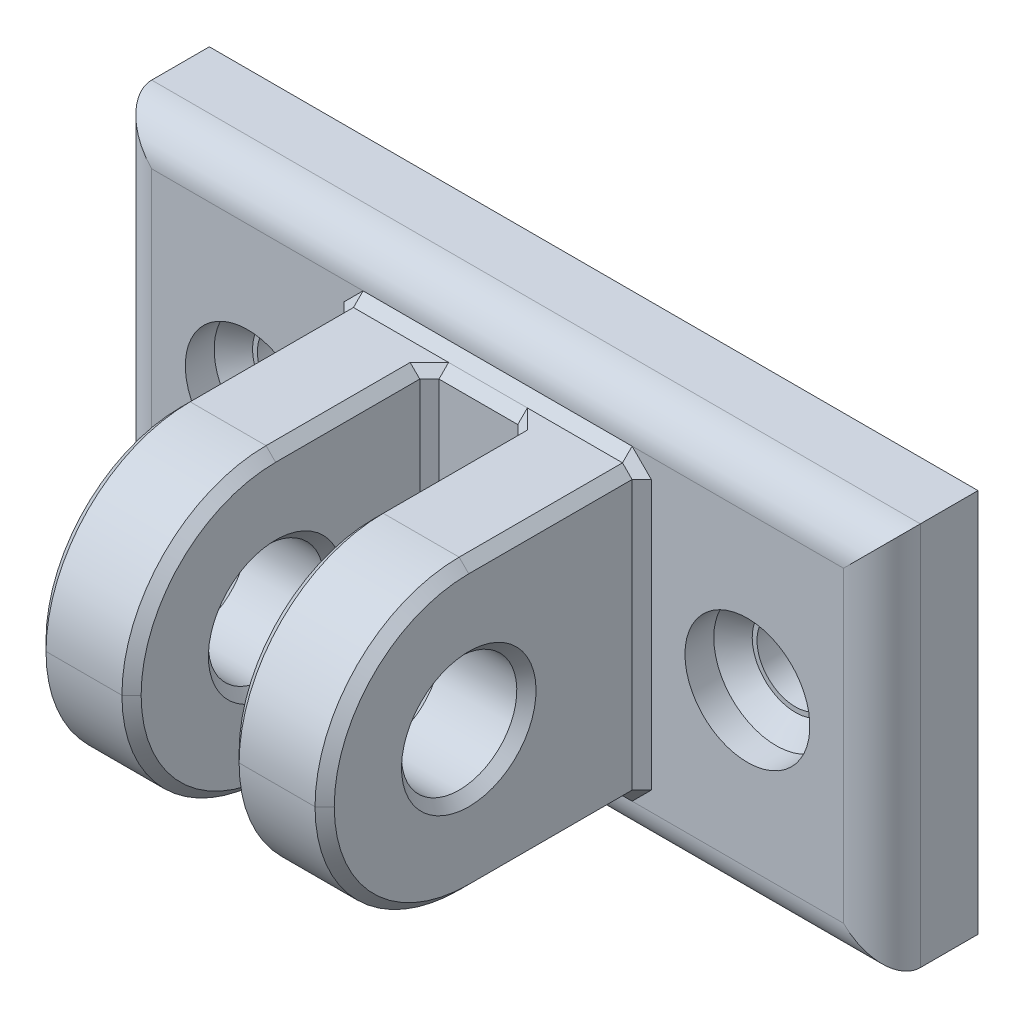
SolidWorks part; units mm, degrees
ref_plane "Front Plane" through (0, 0, 0) normal (0, 0, 1) x (1, 0, 0)
ref_plane "Top Plane" through (0, 0, 0) normal (0, 1, 0) x (1, 0, 0)
ref_plane "Right Plane" through (0, 0, 0) normal (1, 0, 0) x (0, 0, -1)
sketch "Sketch1" plane through (0, 0, 0) normal (0, 0, 1) x (1, 0, 0)
  line L1 (20, 10) -> (-20, 10)
  line L2 (20, 10) -> (20, -10)
  line L3 (20, -10) -> (-20, -10)
  line L4 (-20, 10) -> (-20, -10)
  line L5 (20, 10) -> (-20, -10) construction
  line L6 (20, -10) -> (-20, 10) construction
  point P0 (0, 0)
  dimension "D1" = 20
  dimension "D2" = 40
extrude "Boss-Extrude1" add sketch "Sketch1" along normal blind 5
sketch "Sketch2" plane through (0, 0, 5) normal (0, 0, 1) x (1, 0, 0)
  line L0 (0, 5.7785) -> (0, -5.0624) construction
  line L1 (7.5, -7.5) -> (2.55, 7.5) construction
  line L2 (-7.5, 7.5) -> (-2.55, 7.5)
  line L3 (-7.5, 7.5) -> (-7.5, -7.5)
  line L4 (-7.5, -7.5) -> (-2.55, -7.5)
  line L5 (-2.55, 7.5) -> (-2.55, -7.5)
  line L6 (-7.5, 7.5) -> (-2.55, -7.5) construction
  line L7 (-7.5, -7.5) -> (-2.55, 7.5) construction
  line L8 (7.5, 7.5) -> (2.55, -7.5) construction
  line L9 (2.55, 7.5) -> (2.55, -7.5)
  line L10 (7.5, -7.5) -> (2.55, -7.5)
  line L11 (7.5, 7.5) -> (7.5, -7.5)
  line L12 (7.5, 7.5) -> (2.55, 7.5)
  point P1 (-5.025, 0)
  dimension "D1" = 2.55
  dimension "D2" = 7.5
  dimension "D3" = 15
  dimension "D4" = 0
extrude "Boss-Extrude2" add sketch "Sketch2" along normal blind 16.5
sketch "Sketch3" plane through (-7.5, 0, 0) normal (-1, 0, 0) x (0, 0, 1)
  line L0 (21.5, 7.5) -> (21.5, -7.5) construction
  circle A0 centre (14, 0) radius 3
  dimension "D1" = 6
  dimension "D2" = 7.5
extrude "Cut-Extrude1" cut sketch "Sketch3" against normal through all both and the other way through all
fillet "Fillet1" radius 7.5 4 edges at (5.025, -7.5, 21.5) (5.025, 7.5, 21.5) (-5.025, -7.5, 21.5) (-5.025, 7.5, 21.5)
sketch "Sketch4" plane through (0, 0, 5) normal (0, 0, 1) x (1, 0, 0)
  line L1 (2.55, 7.5) -> (-2.55, 7.5)
  line L2 (2.55, 7.5) -> (2.55, -7.5)
  line L3 (2.55, -7.5) -> (-2.55, -7.5)
  line L4 (-2.55, 7.5) -> (-2.55, -7.5)
extrude "Boss-Extrude3" add sketch "Sketch4" along normal blind 1
chamfer "Chamfer1" distance 0.5 angle 45 28 edges at (-2.55, 0, 6) (2.55, 0, 6) (7.5, 7.5, 9.5) (7.5, 5.3033, 19.3033) (7.5, -5.3033, 19.3033) (7.5, -7.5, 9.5) (7.5, 0, 5) (0, -7.5, 5) (-7.5, -7.5, 9.5) (-7.5, -5.3033, 19.3033) (-7.5, 5.3033, 19.3033) (0, 7.5, 5) (-7.5, 7.5, 9.5) (-7.5, 0, 5) (-2.55, -3, 14) (-7.5, 3, 14) (2.55, 3, 14) (7.5, -3, 14) (-2.55, -5.3033, 19.3033) (-2.55, -7.5, 10) (-2.55, 5.3033, 19.3033) (0, -7.5, 6) (-2.55, 7.5, 10) (2.55, -7.5, 10) (0, 7.5, 6) (2.55, -5.3033, 19.3033) (2.55, 7.5, 10) (2.55, 5.3033, 19.3033)
fillet "Fillet2" radius 2 4 edges at (-20, 0, 5) (0, -10, 5) (20, 0, 5) (0, 10, 5)
sketch "Sketch5" plane through (0, 0, 5) normal (0, 0, 1) x (1, 0, 0)
  line L0 (0, 5.1539) -> (0, -2.3741) construction
  circle A0 centre (-13, 0) radius 2
  circle A1 centre (13, 0) radius 2
  dimension "D1" = 4
  dimension "D2" = 13
extrude "Cut-Extrude2" cut sketch "Sketch5" against normal through all both and the other way through all
sketch "Sketch7" plane through (0, 0, 5) normal (0, 0, 1) x (1, 0, 0)
  line L0 (0, 5.0598) -> (0, -3.6184) construction
  circle A0 centre (-13, 0) radius 3.25
  circle A1 centre (13, 0) radius 3.25
extrude "Cut-Extrude3" cut sketch "Sketch7" against normal blind 2.5
chamfer "Chamfer2" distance 1 angle 45 2 edges at (9.75, 0, 2.5) (-9.75, 0, 2.5)
equation "\"2.5.00mm\"=3"
